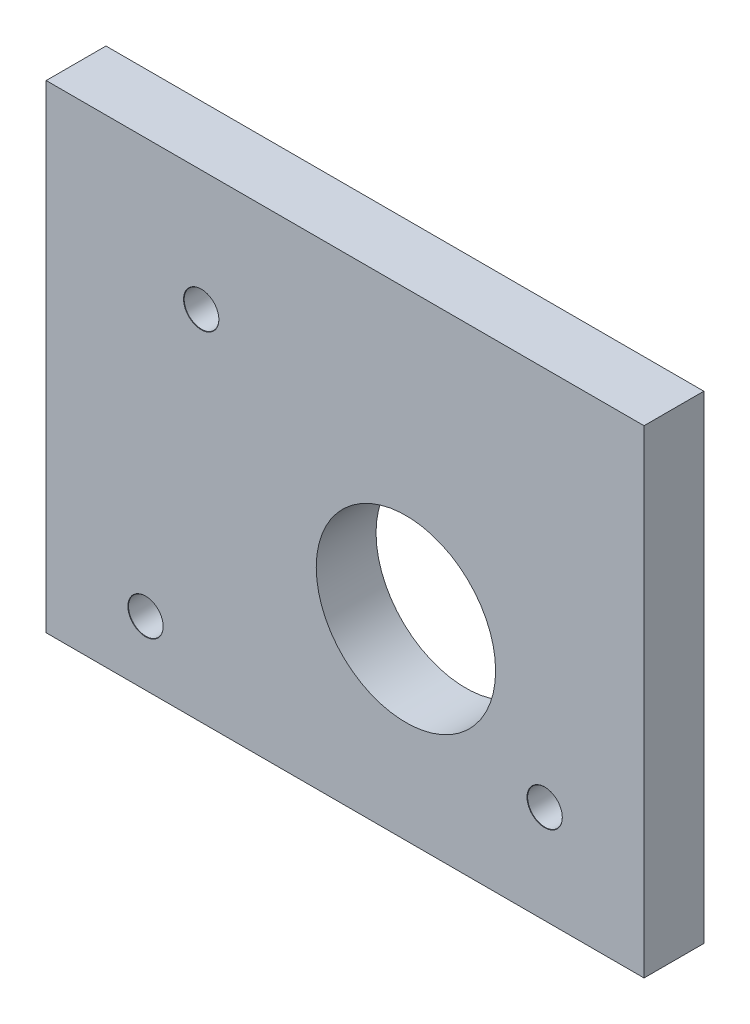
SolidWorks part; units mm, degrees
ref_plane "Front Plane" through (0, 0, 0) normal (0, 0, 1) x (1, 0, 0)
ref_plane "Top Plane" through (0, 0, 0) normal (0, 1, 0) x (1, 0, 0)
ref_plane "Right Plane" through (0, 0, 0) normal (1, 0, 0) x (0, 0, -1)
sketch "hole_reference" plane through (0, 0, 0) normal (0, 0, 1) x (1, 0, 0)
  line L0 (0, 0) -> (33.3777, 0) construction
  line L1 (33.3777, 0) -> (33.3777, 2.86) construction
  point P0 (0, 0)
  point P1 (33.3777, 2.86)
  point P3 (4.6551, 24.5628)
  point P4 (21.7754, 10.6949)
  dimension "D1" = 33.5
  dimension "D2" = 25
  dimension "D3" = 36
  dimension "D4" = 2.86
  dimension "D5" = 14
  dimension "D6" = 24.26
sketch "Sketch1" plane through (0, 0, 0) normal (0, 0, 1) x (1, 0, 0)
  line L0 (4.6551, 24.5628) -> (4.6551, 0) construction
  line L1 (-8.3112, 34.6544) -> (41.6888, 34.6544)
  line L2 (-8.3112, 34.6544) -> (-8.3112, -5.3456)
  line L3 (-8.3112, -5.3456) -> (41.6888, -5.3456)
  line L4 (41.6888, 34.6544) -> (41.6888, -5.3456)
  line L5 (0, 0) -> (33.3777, 0) construction
  line L8 (16.6888, 0) -> (16.6888, -5.3456) construction
  dimension "D1" = 40
  dimension "D2" = 50
  dimension "D3" = 10.0916
extrude "Boss-Extrude1" add sketch "Sketch1" along normal mid plane 5 contours L1 L4 L3 L2
hole_wizard "M2.5 Clearance Hole2" positions "Sketch2" profile "Sketch3" hole size "M2.5" standard "ANSI Metric" end condition through all
sketch "Sketch2" plane through (0, 0, 2.5) normal (0, 0, 1) x (1, 0, 0)
  point P0 (4.6551, 24.5628)
  point P6 (33.3777, 2.86)
  point P19 (0, 0)
sketch "Sketch3" plane through (4.6551, 24.5628, 2.5) normal (1, 0, 0) x (0, -1, 0)
  line L0 (0, 0) -> (0, 5)
  line L1 (0, 5) -> (1.45, 5)
  line L2 (1.45, 5) -> (1.45, 0.025)
  line L3 (1.45, 0.025) -> (1.475, 0)
  line L5 (1.475, 0) -> (0, 0)
  line L6 (-1.45, 0.025) -> (-1.475, 0) construction
  line L11 (0, -6.35) -> (0, 107.95) construction
  dimension "Thru Hole Dia." = 2.9
  dimension "Thru Hole Depth" = 5
  dimension "Near C'Sink Dia." = 2.95
  dimension "Near C'Sink Angle" = 90
sketch "Sketch4" plane through (0, 0, 2.5) normal (0, 0, 1) x (1, 0, 0)
  circle A0 centre (21.7754, 10.6949) radius 7.5
  dimension "D1" = 15
extrude "Cut-Extrude1" cut sketch "Sketch4" against normal through all
ref_axis "Axis1" through (21.7754, 10.6949, -2.5) along (0, 0, 1)
ref_plane "Plane1" through (0, 14.6544, 0) normal (0, 1, 0) x (1, 0, 0)
ref_plane "Plane2" through (21.7754, 0, 0) normal (1, 0, 0) x (0, 0, -1)
